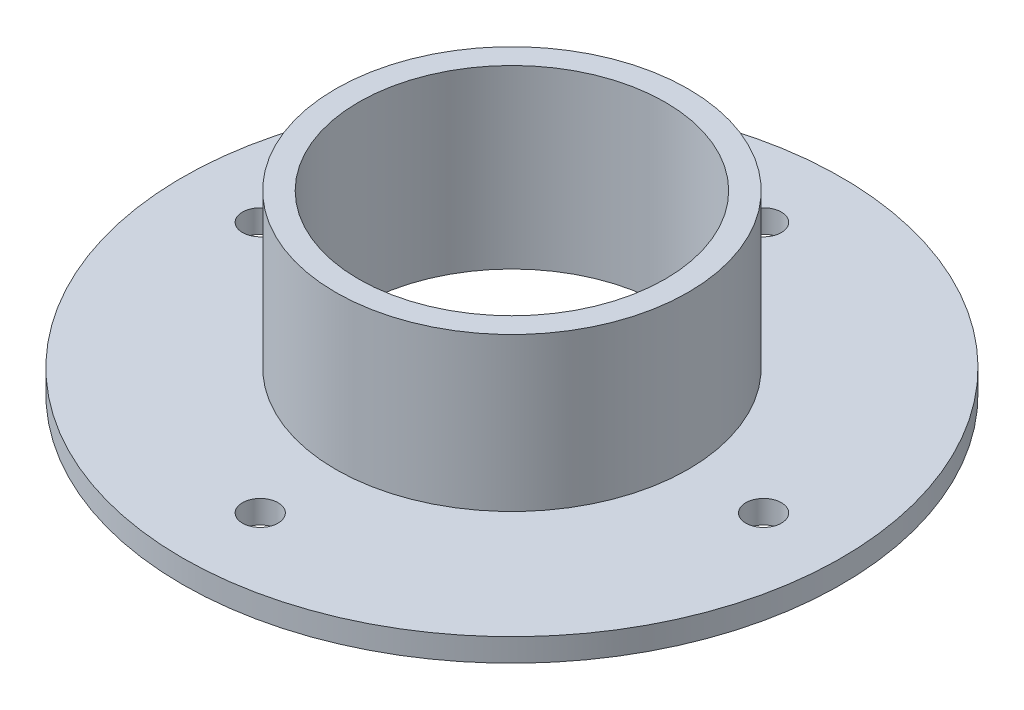
SolidWorks part; units mm, degrees
ref_plane "前视基准面" through (0, 0, 0) normal (0, 0, 1) x (1, 0, 0)
ref_plane "上视基准面" through (0, 0, 0) normal (0, 1, 0) x (1, 0, 0)
ref_plane "右视基准面" through (0, 0, 0) normal (1, 0, 0) x (0, 0, -1)
sketch "草图1" plane through (0, 0, 0) normal (0, 1, 0) x (1, 0, 0)
  circle A0 centre (0, 0) radius 43
  dimension "D1" = 86
extrude "凸台-拉伸1" add sketch "草图1" along normal blind 3
sketch "草图2" plane through (0, 3, 0) normal (0, 1, 0) x (1, 0, 0)
  circle A0 centre (0, 0) radius 23
  circle A1 centre (0, 0) radius 20
  dimension "D1" = 3
  dimension "D2" = 40
extrude "凸台-拉伸2" add sketch "草图2" along normal blind 20
sketch "草图3" plane through (0, 3, 0) normal (0, 1, 0) x (1, 0, 0)
  circle A0 centre (0, 0) radius 20
  circle A1 centre (0, 32.8377) radius 2.3202
  circle A2 centre (32.8377, 0) radius 2.3202
  circle A3 centre (0, -32.8377) radius 2.3202
  circle A4 centre (-32.8377, 0) radius 2.3202
  point P14 (0, 0)
  dimension "D1" = 4
extrude "切除-拉伸1" cut sketch "草图3" against normal blind 20
